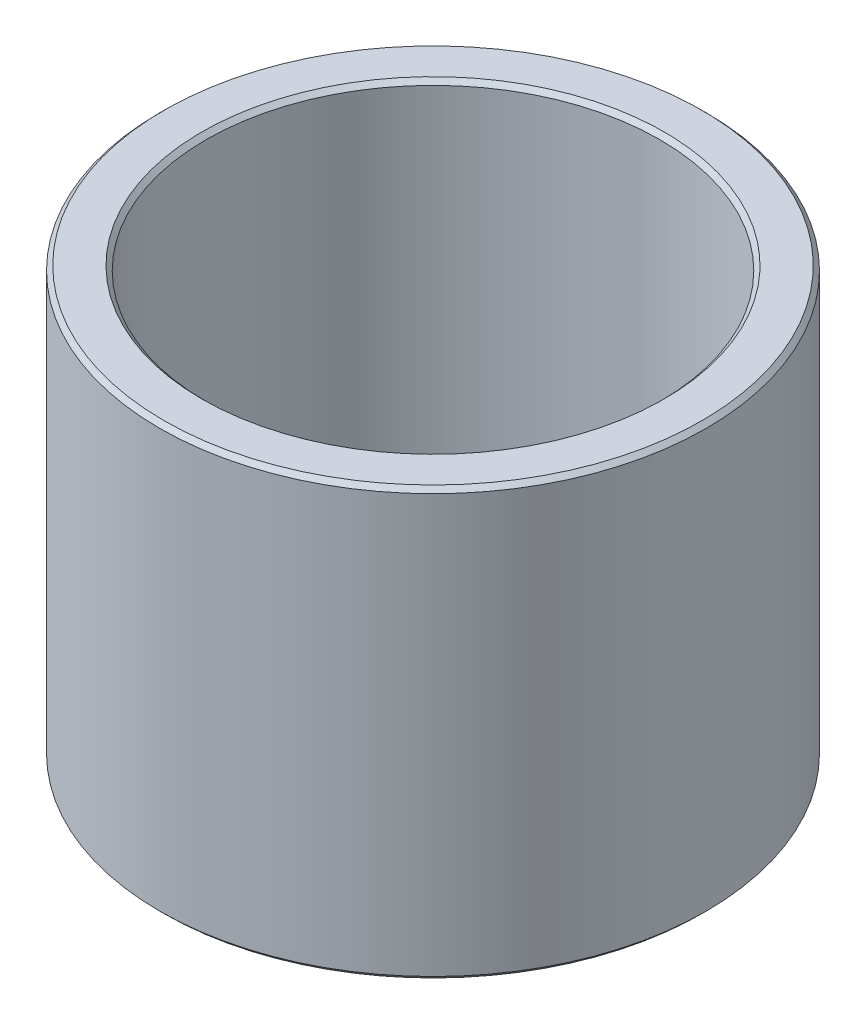
SolidWorks part; units mm, degrees
ref_plane "Front Plane" through (0, 0, 0) normal (0, 0, 1) x (1, 0, 0)
ref_plane "Top Plane" through (0, 0, 0) normal (0, 1, 0) x (1, 0, 0)
ref_plane "Right Plane" through (0, 0, 0) normal (1, 0, 0) x (0, 0, -1)
sketch "Sketch1" plane through (0, 0, 0) normal (0, 1, 0) x (1, 0, 0)
  circle A0 centre (0, 0) radius 42.5
  dimension "SLEEVE_OD" = 85
extrude "Boss-Extrude1" add sketch "Sketch1" along normal blind 66.3926
sketch "Sketch2" plane through (0, 0, 0) normal (0, 1, 0) x (1, 0, 0)
  circle A0 centre (0, 0) radius 35.2749
  dimension "BORE_D" = 70.5497
extrude "Cut-Extrude1" cut sketch "Sketch2" along normal through all
chamfer "Chamfer1" distance 0.6865 angle 45 4 edges at (0, 66.3926, 35.2749) (0, 0, 35.2749) (0, 0, 42.5) (0, 66.3926, 42.5)
